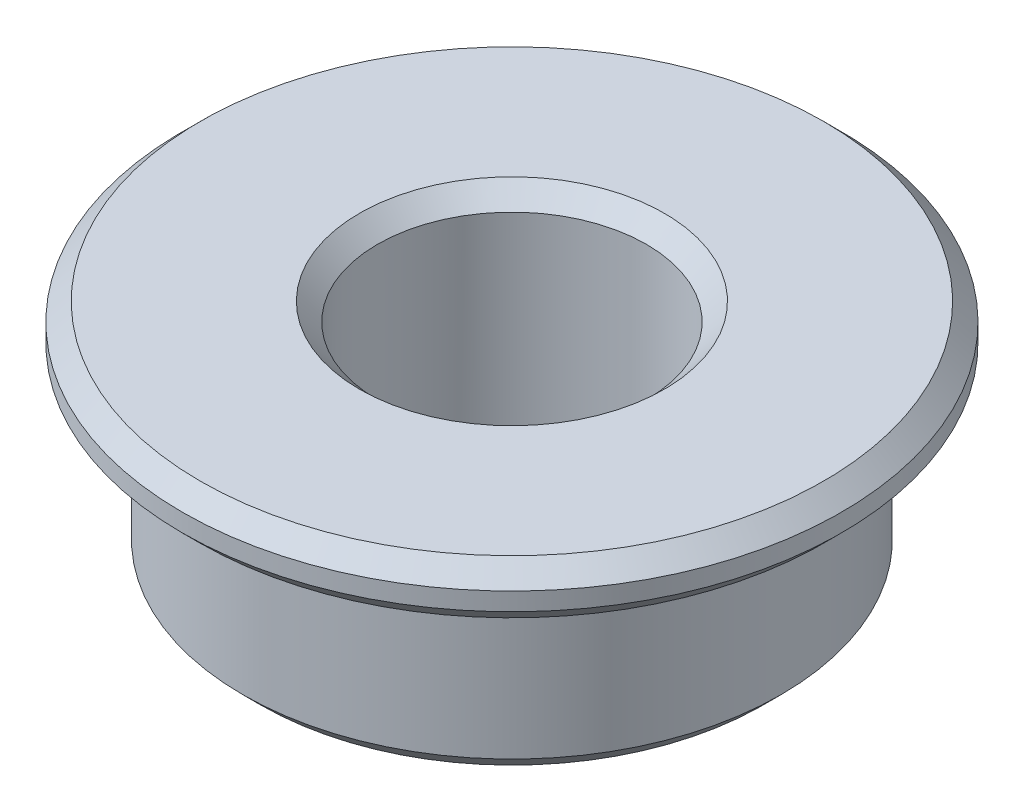
SolidWorks part; units mm, degrees
ref_plane "正面" through (0, 0, 0) normal (0, 0, 1) x (1, 0, 0)
ref_plane "平面" through (0, 0, 0) normal (0, 1, 0) x (1, 0, 0)
ref_plane "右側面" through (0, 0, 0) normal (1, 0, 0) x (0, 0, -1)
sketch "ｽｹｯﾁ1" plane through (0, 0, 0) normal (0, 1, 0) x (1, 0, 0)
  circle A0 centre (0, 0) radius 3.675
  circle A1 centre (0, 0) radius 1.5
  dimension "D1" = 7.35
  dimension "D2" = 3
extrude "ﾎﾞｽ - 押し出し1" add sketch "ｽｹｯﾁ1" along normal blind 0.6
sketch "ｽｹｯﾁ2" plane through (0, 0, 0) normal (0, -1, 0) x (1, 0, 0)
  circle A0 centre (0, 0) radius 1.5 construction
  circle A1 centre (0, 0) radius 1.5
  circle A2 centre (0, 0) radius 3
  dimension "D1" = 6
extrude "ﾎﾞｽ - 押し出し2" add sketch "ｽｹｯﾁ2" along normal blind 1.9
chamfer "面取り1" distance 0.2 angle 45 5 edges at (0, -1.9, -1.5) (0, -1.9, -3) (0, 0.6, 1.5) (0, 0.6, 3.675) (0, 0, 3.675)
